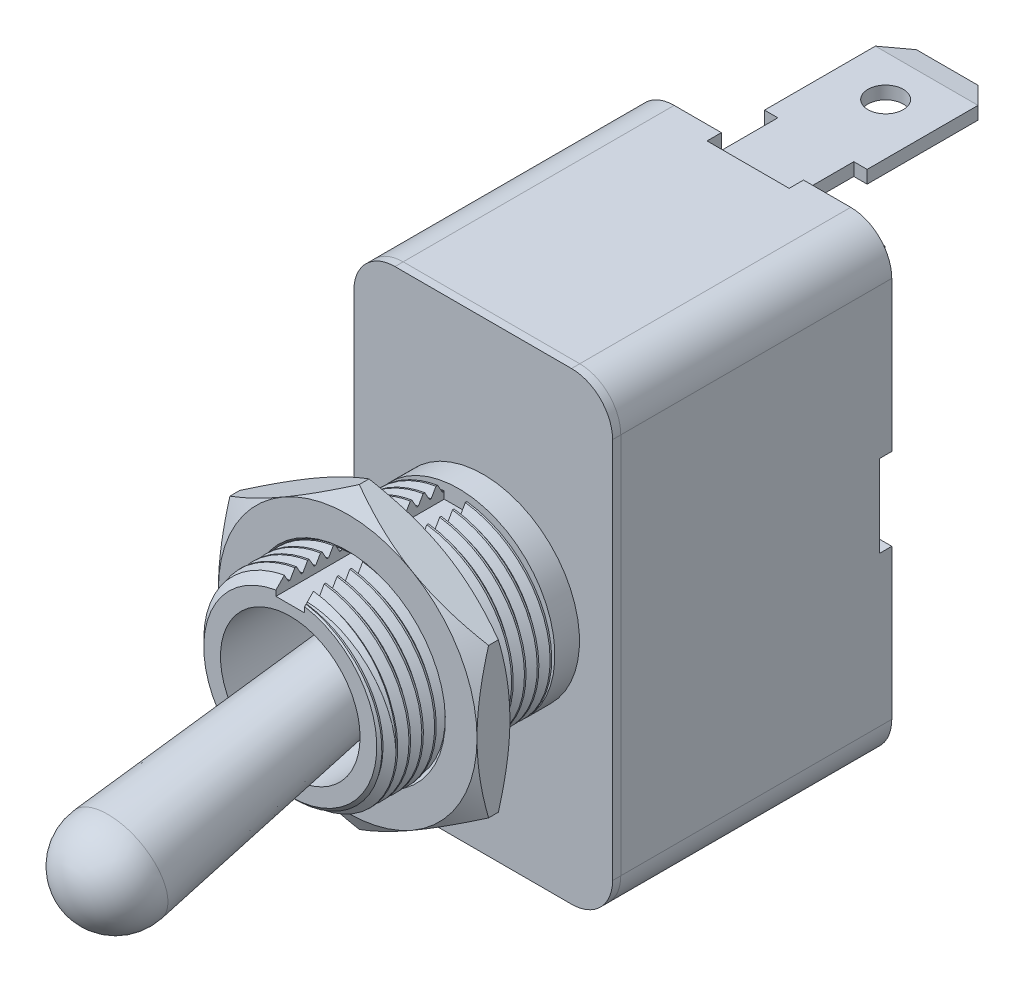
SolidWorks part; units mm, degrees
ref_plane "Front Plane" through (0, 0, 0) normal (0, 0, 1) x (1, 0, 0)
ref_plane "Top Plane" through (0, 0, 0) normal (0, 1, 0) x (1, 0, 0)
ref_plane "Right Plane" through (0, 0, 0) normal (1, 0, 0) x (0, 0, -1)
sketch "Sketch1" plane through (0, 0, 0) normal (0, 1, 0) x (1, 0, 0)
  line L0 (-9.144, 0) -> (9.144, 0) construction
  line L1 (14.351, -8.001) -> (-14.351, -8.001) construction
  line L2 (14.351, -8.001) -> (14.351, 8.001) construction
  line L3 (14.351, 8.001) -> (-14.351, 8.001) construction
  line L4 (-14.351, -8.001) -> (-14.351, 8.001) construction
  line L5 (14.351, -8.001) -> (-14.351, 8.001) construction
  line L6 (14.351, 8.001) -> (-14.351, -8.001) construction
  circle A0 centre (0, 0) radius 5.9531 construction
  point P0 (0, 0)
  point P8 (-5.9531, 0)
  point P9 (0, -5.9531)
  dimension "D3" = 9.144
  dimension "Thread OD" = 11.9062
  dimension "D1" = 28.702
  dimension "D2" = 16.002
sketch "Sketch2" plane through (0, 0, 0) normal (0, 0, 1) x (1, 0, 0)
  line L0 (0, 0) -> (0, 11.938) construction
  line L1 (14.351, 0) -> (-14.351, 0) construction
  line L2 (0, 11.938) -> (0, 26.162) construction
  line L3 (0, 0) -> (0, -17.272) construction
  line L4 (-14.351, 0) -> (14.351, 0) construction
  line L5 (0, -17.272) -> (0, -28.702) construction
  line L6 (-5.9531, 11.938) -> (5.9531, 11.938) construction
  line L7 (-3.048, 26.162) -> (3.048, 26.162) construction
  line L8 (-14.351, -17.272) -> (14.351, -17.272) construction
  line L9 (-5.9531, 11.938) -> (-5.9531, 11.1442) construction
  line L10 (-14.351, -28.702) -> (14.351, -28.702) construction
  point P15 (0, 1.524)
  dimension "D1" = 11.938
  dimension "D2" = 14.224
  dimension "D3" = 17.272
  dimension "D4" = 11.43
  dimension "D5" = 28.702
  dimension "D6" = 6.096
  dimension "Thread Height" = 10.414
  dimension "Thread Pitch" = 0.7937
sketch "Sketch3" plane through (0, 0, 0) normal (1, 0, 0) x (0, 0, -1)
  line L0 (-8.001, -17.272) -> (8.001, -17.272) construction
  line L1 (-8.001, 0) -> (8.001, 0) construction
  line L2 (-5.9531, 11.938) -> (5.9531, 11.938) construction
ref_plane "Plane1" through (0, 11.938, 0) normal (0, 1, 0) x (-1, 0, 0)
sketch "Sketch4" plane through (0, 11.938, 0) normal (0, 1, 0) x (-1, 0, 0)
  circle A0 centre (0, 0) radius 5.9531 construction
  circle A1 centre (0, 0) radius 5.9531
extrude "Boss-Extrude1" add sketch "Sketch4" against normal up to vertex (10.414 mm away) up to point (0, 1.524, 0)
sketch "Sketch5" plane through (0, 11.938, 0) normal (0, 1, 0) x (1, 0, 0)
  circle A1 centre (0, 0) radius 5.9531
  circle A2 centre (0, 0) radius 5.9531
  point P0 (-5.9531, 0)
  dimension "D1" = 0
curve "Helix/Spiral1" pitch 0.7937 height 11.2077 turns 14.12
sketch "Sketch6" plane through (0, 0, 0) normal (0, 0, 1) x (1, 0, 0)
  line L0 (-6.0391, 12.6821) -> (-6.0391, 11.8884) construction
  line L1 (-6.0391, 11.8884) -> (-5.3516, 12.2853) construction
  line L2 (-5.3516, 12.2853) -> (-6.0391, 12.6821) construction
  line L3 (-5.4376, 12.3349) -> (-5.4376, 12.2357)
  line L4 (-5.9531, 12.6325) -> (-5.9531, 11.938) construction
  line L5 (-5.3516, 12.2853) -> (-5.4376, 12.2853) construction
  line L6 (-5.9531, 12.2853) -> (-6.0391, 12.2853) construction
  line L7 (-5.4376, 12.2357) -> (-5.9961, 11.9132)
  line L8 (-5.9961, 11.9132) -> (-5.9961, 12.6573)
  line L9 (-5.9961, 12.6573) -> (-5.4376, 12.3349)
  point P13 (-5.9961, 12.2853)
  dimension "D1" = 0.7937
  dimension "D2" = 0.0992
sweep "Cut-Sweep1" cut profiles "Sketch6" path "Helix/Spiral1"
sketch "Sketch7" plane through (0, 11.938, 0) normal (0, 1, 0) x (1, 0, 0)
  circle A0 centre (0, 0) radius 5.3516
extrude "Cut-Extrude1" cut sketch "Sketch7" against normal up to vertex (10.414 mm away) draft 45 flip side to cut up to point (0, 1.524, 0)
sketch "Sketch8" plane through (0, 1.524, 0) normal (0, -1, 0) x (1, 0, 0)
  circle A2 centre (0, 0) radius 5.9531
  circle A3 centre (0, 0) radius 5.9531
  dimension "D2" = 0
extrude "Boss-Extrude2" add sketch "Sketch8" along normal up to vertex (1.524 mm away) up to point (0, 0, 0)
sketch "Sketch9" plane through (0, 0, 0) normal (0, -1, 0) x (1, 0, 0)
  line L0 (14.351, 8.001) -> (-14.351, 8.001) construction
  line L1 (-14.351, 8.001) -> (-14.351, -8.001) construction
  line L2 (14.351, -8.001) -> (-14.351, -8.001) construction
  line L3 (14.351, 8.001) -> (14.351, -8.001) construction
  line L4 (11.811, 8.001) -> (-11.811, 8.001)
  line L5 (-14.351, 5.461) -> (-14.351, -5.461)
  line L6 (11.811, -8.001) -> (-11.811, -8.001)
  line L7 (14.351, 5.461) -> (14.351, -5.461)
  arc A0 (11.811, 8.001) -> (14.351, 5.461) centre (11.811, 5.461) cw
  arc A1 (11.811, -8.001) -> (14.351, -5.461) centre (11.811, -5.461) ccw
  arc A2 (-14.351, -5.461) -> (-11.811, -8.001) centre (-11.811, -5.461) ccw
  arc A3 (-11.811, 8.001) -> (-14.351, 5.461) centre (-11.811, 5.461) ccw
  dimension "D1" = 2.54
extrude "Boss-Extrude3" add sketch "Sketch9" along normal blind 0.508
sketch "Sketch10" plane through (0, 11.938, 0) normal (0, 1, 0) x (1, 0, 0)
  line L0 (-5.9531, 0) -> (5.9531, 0) construction
  circle A0 centre (0, 0) radius 4.318
  dimension "D1" = 8.636
extrude "Cut-Extrude2" cut sketch "Sketch10" against normal up to surface (11.938 mm away) up to face at (0, 0, -5.9531)
sketch "Sketch11" plane through (0, 11.938, 0) normal (0, 1, 0) x (1, 0, 0)
  line L0 (4.9371, 0.889) -> (4.9371, -0.889)
  line L1 (4.9371, 0.889) -> (5.8864, 0.889)
  line L2 (4.9371, -0.889) -> (5.8864, -0.889)
  line L3 (0, 0) -> (5.9531, 0) construction
  circle A0 centre (0, 0) radius 5.9531 construction
  arc A1 (5.8864, -0.889) -> (5.8864, 0.889) centre (0, 0) ccw
  dimension "D1" = 1.016
  dimension "D2" = 1.778
extrude "Cut-Extrude3" cut sketch "Sketch11" against normal up to vertex (10.414 mm away) up to point (0, 1.524, 0)
sketch "Sketch12" plane through (0, 0, 0) normal (0, 0, 1) x (1, 0, 0)
  line L0 (0, 11.938) -> (0, 26.162) construction
  line L1 (0, 0) -> (0, 26.162) construction
  line L2 (-14.351, 0) -> (14.351, 0) construction
  line L3 (0, 4.826) -> (-2.2147, 4.826)
  line L4 (-2.2147, 4.826) -> (-3.0448, 22.9747)
  line L5 (0, 26.162) -> (0, 4.826)
  line L6 (-3.048, 26.162) -> (-3.048, 23.114) construction
  line L7 (-5.9531, 11.938) -> (5.9531, 11.938) construction
  arc A0 (0, 26.162) -> (-3.0448, 22.9747) centre (0, 23.114) ccw
  point P11 (-2.54, 11.938)
  dimension "D1" = 7.112
  dimension "D2" = 5.08
revolve "Revolve1" add sketch "Sketch12" angle 360 mid plane about L1
sketch "Sketch13" plane through (0, -0.508, 0) normal (0, -1, 0) x (1, 0, 0)
  line L4 (11.811, 8.001) -> (-11.811, 8.001)
  line L5 (-14.351, 5.461) -> (-14.351, -5.461)
  line L6 (-11.811, -8.001) -> (11.811, -8.001)
  line L7 (14.351, -5.461) -> (14.351, 5.461)
  line L8 (11.811, 8.001) -> (-11.811, 8.001)
  line L9 (-14.351, 5.461) -> (-14.351, -5.461)
  line L10 (-11.811, -8.001) -> (11.811, -8.001)
  line L11 (14.351, -5.461) -> (14.351, 5.461)
  arc A4 (14.351, 5.461) -> (11.811, 8.001) centre (11.811, 5.461) ccw
  arc A5 (-11.811, 8.001) -> (-14.351, 5.461) centre (-11.811, 5.461) ccw
  arc A6 (-14.351, -5.461) -> (-11.811, -8.001) centre (-11.811, -5.461) ccw
  arc A7 (11.811, -8.001) -> (14.351, -5.461) centre (11.811, -5.461) ccw
  arc A8 (14.351, 5.461) -> (11.811, 8.001) centre (11.811, 5.461) ccw
  arc A9 (-11.811, 8.001) -> (-14.351, 5.461) centre (-11.811, 5.461) ccw
  arc A10 (-14.351, -5.461) -> (-11.811, -8.001) centre (-11.811, -5.461) ccw
  arc A11 (11.811, -8.001) -> (14.351, -5.461) centre (11.811, -5.461) ccw
  dimension "D1" = 0
extrude "Boss-Extrude4" add sketch "Sketch13" along normal up to vertex (16.764 mm away) separate body up to point (0, -17.272, 0)
sketch "Sketch14" plane through (0, -17.272, 0) normal (0, -1, 0) x (1, 0, 0)
  line L0 (0, -8.001) -> (0, 8.001) construction
  line L1 (-14.351, 0) -> (14.351, 0) construction
  line L2 (14.351, 8.001) -> (-14.351, 8.001) construction
  line L4 (-14.351, 2.54) -> (-5.969, 2.54)
  line L5 (-14.351, 2.54) -> (-14.351, -2.54)
  line L6 (-14.351, -2.54) -> (-5.969, -2.54)
  line L7 (-5.969, 2.54) -> (-5.969, -2.54)
  line L8 (-2.54, 8.001) -> (2.54, 8.001) construction
  line L9 (-2.54, 8.001) -> (-2.54, -8.001) construction
  line L10 (-2.54, -8.001) -> (2.54, -8.001) construction
  line L14 (2.54, 8.001) -> (2.54, -8.001) construction
  line L15 (-14.351, 5.461) -> (-14.351, -5.461) construction
  line L16 (5.969, 2.54) -> (5.969, -2.54)
  line L17 (14.351, -2.54) -> (5.969, -2.54)
  line L18 (14.351, 2.54) -> (14.351, -2.54)
  line L19 (14.351, 2.54) -> (5.969, 2.54)
  dimension "D2" = 5.08
  dimension "D3" = 8.382
  dimension "D1" = 5.08
extrude "Cut-Extrude4" cut sketch "Sketch14" against normal blind 0.889
sketch "Sketch15" plane through (0, -17.272, 0) normal (0, -1, 0) x (1, 0, 0)
  line L1 (-2.54, 8.001) -> (-2.54, -8.001) construction
  line L2 (-2.54, 8.001) -> (2.54, 8.001) construction
  line L3 (2.54, 8.001) -> (2.54, -8.001) construction
  line L4 (-2.54, -8.001) -> (2.54, -8.001) construction
  line L5 (-2.54, 8.001) -> (-2.54, -8.001)
  line L6 (-2.54, 8.001) -> (2.54, 8.001)
  line L7 (2.54, 8.001) -> (2.54, -8.001)
  line L9 (-2.54, -8.001) -> (2.54, -8.001)
extrude "Cut-Extrude5" cut sketch "Sketch15" against normal blind 0.762
sketch "Sketch16" plane through (0, -16.383, 0) normal (0, -1, 0) x (1, 0, 0)
  line L0 (13.589, 2.3495) -> (13.589, -2.3495)
  line L1 (7.239, 2.3495) -> (13.589, 2.3495)
  line L2 (7.239, 2.3495) -> (7.239, -2.3495)
  line L3 (7.239, -2.3495) -> (13.589, -2.3495)
  line L4 (7.239, 0) -> (13.589, 0) construction
  circle A0 centre (9.144, 0) radius 1.524 construction
  dimension "D1" = 3.048
  dimension "D2" = 4.699
  dimension "D3" = 6.35
  dimension "D4" = 1.905
extrude "Boss-Extrude5" add sketch "Sketch16" along normal blind 0.7937 separate body
sketch "Sketch17" plane through (13.589, 0, 0) normal (-1, 0, 0) x (0, 0, 1)
  line L0 (-3.175, -28.702) -> (3.175, -28.702)
  line L1 (0, -16.383) -> (0, -28.702) construction
  line L4 (2.3495, -16.383) -> (-2.3495, -16.383)
  line L5 (-2.3495, -16.383) -> (-2.3495, -17.1767)
  line L6 (-2.3495, -17.1767) -> (2.3495, -17.1767)
  line L7 (2.3495, -17.1767) -> (2.3495, -16.383)
  line L8 (2.3495, -16.383) -> (-2.3495, -16.383)
  line L9 (-2.3495, -16.383) -> (-2.3495, -20.574)
  line L11 (2.3495, -20.574) -> (2.3495, -16.383)
  line L12 (-3.175, -20.574) -> (-2.3495, -20.574)
  line L13 (-3.175, -20.574) -> (-3.175, -28.702)
  line L16 (3.175, -20.574) -> (3.175, -28.702)
  line L17 (3.175, -20.574) -> (2.3495, -20.574)
  circle A1 centre (0, -24.892) radius 1.0922
  dimension "D2" = 2.1844
  dimension "D3" = 6.35
  dimension "D4" = 8.128
  dimension "D8" = 3.81
  dimension "D1" = 0
extrude "Boss-Extrude6" add sketch "Sketch17" along normal blind 0.7937
chamfer "Chamfer1" distance 1.27 distance2 1.27 2 edges at (13.1921, -28.702, -3.175) (13.1921, -28.702, 3.175)
chamfer "Chamfer2" distance 1.27 distance2 0.1905 2 edges at (13.589, -28.702, 0) (12.7953, -28.702, 0)
mirror "Mirror1" [suppressed] about plane through (0, 0, 0) normal (1, 0, 0)
sketch "Sketch18" plane through (0, -16.51, 0) normal (0, -1, 0) x (1, 0, 0)
  line L0 (-2.3495, -4.445) -> (-2.3495, 1.905)
  line L1 (2.3495, -4.445) -> (2.3495, 1.905)
  line L2 (2.3495, 1.905) -> (-2.3495, 1.905)
  line L3 (0, 1.905) -> (0, -4.445) construction
  line L4 (-2.3495, -4.445) -> (2.3495, -4.445)
  circle A0 centre (0, 0) radius 1.524 construction
  dimension "D3" = 3.048
  dimension "D1" = 6.35
  dimension "D2" = 4.699
  dimension "D4" = 1.905
extrude "Boss-Extrude7" add sketch "Sketch18" along normal blind 0.7937 separate body
sketch "Sketch19" plane through (0, 0, -4.445) normal (0, 0, 1) x (1, 0, 0)
  line L0 (3.175, -28.702) -> (-3.175, -28.702)
  line L1 (-3.175, -28.702) -> (-3.175, -20.574)
  line L2 (-3.175, -20.574) -> (-2.3495, -20.574)
  line L4 (2.3495, -16.51) -> (-2.3495, -16.51)
  line L5 (-2.3495, -16.51) -> (-2.3495, -17.3038)
  line L6 (-2.3495, -17.3038) -> (2.3495, -17.3038)
  line L7 (2.3495, -17.3038) -> (2.3495, -16.51)
  line L8 (2.3495, -16.51) -> (-2.3495, -16.51)
  line L9 (-2.3495, -16.51) -> (-2.3495, -20.574)
  line L11 (2.3495, -20.574) -> (2.3495, -16.51)
  line L13 (0, -28.702) -> (0, -16.51) construction
  line L17 (3.175, -20.574) -> (2.3495, -20.574)
  line L18 (3.175, -28.702) -> (3.175, -20.574)
  circle A1 centre (0, -24.892) radius 1.0922
  dimension "D2" = 2.1844
  dimension "D3" = 6.35
  dimension "D5" = 8.128
  dimension "D8" = 3.81
  dimension "D1" = 0
extrude "Boss-Extrude8" add sketch "Sketch19" along normal blind 0.7937
chamfer "Chamfer3" distance 1.27 distance2 1.27 2 edges at (3.175, -28.702, -4.0481) (-3.175, -28.702, -4.0481)
chamfer "Chamfer4" distance 0.1905 distance2 1.27 2 edges at (0, -28.702, -3.6512) (0, -28.702, -4.445)
sketch "Sketch20" plane through (0, 11.938, 0) normal (0, 1, 0) x (1, 0, 0)
  line L1 (4.6194, 8.001) -> (-4.6194, 8.001)
  line L2 (-4.6194, 8.001) -> (-9.2388, 0)
  line L3 (-9.2388, 0) -> (-4.6194, -8.001)
  line L4 (-4.6194, -8.001) -> (4.6194, -8.001)
  line L5 (4.6194, -8.001) -> (9.2388, 0)
  line L6 (9.2388, 0) -> (4.6194, 8.001)
  circle A0 centre (0, 0) radius 8.001 construction
  circle A1 centre (0, 0) radius 5.4376
  point P10 (-8.001, 0)
  dimension "D1" = 16.002
extrude "Boss-Extrude9" add sketch "Sketch20" along normal blind 2.032 from offset 5.585 separate body offset against normal yes
sketch "Sketch21" plane through (0, 0, 0) normal (0, 0, 1) x (1, 0, 0)
  line L0 (-5.4376, 8.385) -> (-5.4376, 7.7835)
  line L1 (-5.4376, 7.7835) -> (-6.0391, 8.385)
  line L2 (-6.0391, 8.385) -> (-5.4376, 8.385)
  line L5 (-6.0391, 12.6821) -> (-6.0391, 11.8884) construction
  line L6 (0, 8.385) -> (0, 6.353) construction
  line L7 (5.4376, 8.385) -> (-5.4376, 8.385) construction
  line L8 (-5.4376, 6.353) -> (5.4376, 6.353) construction
  line L9 (-9.2388, 8.385) -> (-8.001, 8.385)
  line L10 (-8.001, 8.385) -> (-9.2388, 7.6704)
  line L11 (-9.2388, 7.6704) -> (-9.2388, 8.385)
  line L12 (-5.4376, 6.9545) -> (-5.4376, 6.353)
  line L13 (-5.4376, 6.353) -> (-6.0391, 6.353)
  line L14 (-6.0391, 6.353) -> (-5.4376, 6.9545)
  line L15 (-9.2388, 6.353) -> (-9.2388, 7.0676)
  line L16 (-9.2388, 7.0676) -> (-8.001, 6.353)
  line L17 (-8.001, 6.353) -> (-9.2388, 6.353)
  dimension "D1" = 45
  dimension "D2" = 30
revolve "Cut-Revolve1" cut sketch "Sketch21" angle 360 mid plane about L6
move or copy body "Body-Move/Copy1" bodies to move or copy 115 109 129 122 126 131 copy no rotation origin (2.678, -3.4086, 0.7306) rotation axis (0.5774, 0.5774, 0.5774) rotation angle 120
sketch "Sketch22" plane through (0, 0, 0) normal (1, 0, 0) x (0, 0, -1)
  arc A0 (-27.1139, -3.0417) -> (-27.1139, -9.1314) centre (-27.2532, -6.0865) ccw construction
  point P0 (-30.3012, -6.0865)
sketch "Sketch23" plane through (0, 0, 0) normal (1, 0, 0) x (0, 0, -1)
  line L0 (-15.9587, -3.552) -> (-27.1139, -3.0417)
  line L1 (-8.9652, -3.8718) -> (-27.1139, -3.0417) construction
  line L2 (-27.1139, -9.1314) -> (-15.8818, -8.6176)
  line L3 (-27.1139, -9.1314) -> (-8.9652, -8.3012) construction
  arc A0 (-27.1139, -3.0417) -> (-27.1139, -9.1314) centre (-27.2532, -6.0865) ccw
  spline S0 degree 3 poles (-15.9913, -1.847) (-15.9819, -2.246) (-15.9729, -2.736) (-15.9586, -3.5521) (-15.9538, -3.8403) (-15.9441, -4.442) (-15.9393, -4.7492) (-15.93, -5.3761) (-15.9253, -5.6983) (-15.9164, -6.344) (-15.9119, -6.6638) (-15.9026, -7.2971) (-15.8978, -7.6136) (-15.8883, -8.225) (-15.8835, -8.5186) (-15.8741, -9.0819) (-15.8694, -9.3541) (-15.8603, -9.8584) (-15.856, -10.0907) (-15.847, -10.5169) (-15.8424, -10.7122) (-15.833, -11.0509) (-15.8283, -11.1954) (-15.8189, -11.4352) (-15.8142, -11.5308) (-15.805, -11.6651) (-15.8005, -11.7049) (-15.7917, -11.73) (-15.7873, -11.7148) (-15.7782, -11.6303) (-15.7736, -11.5616) (-15.7644, -11.371) (-15.7596, -11.2477) (-15.7504, -10.9558) (-15.7458, -10.7868) (-15.7369, -10.4025) (-15.7325, -10.1853) (-15.7238, -9.7197) (-15.7194, -9.47) (-15.7103, -8.9366) (-15.7056, -8.6511) (-15.6964, -8.066) (-15.6919, -7.7644) (-15.6828, -7.1429) (-15.6782, -6.821) (-15.6696, -6.1819) (-15.6654, -5.8621) (-15.6567, -5.222) (-15.6521, -4.9) (-15.6431, -4.2781) (-15.6385, -3.9757) (-15.6295, -3.3879) (-15.6249, -3.1009) (-15.616, -2.5645) (-15.6116, -2.3127) (-15.6032, -1.8416) (-15.5989, -1.6212) (-15.5901, -1.2283) (-15.5857, -1.0539) (-15.5767, -0.7494) (-15.5721, -0.6186) (-15.5632, -0.4108) (-15.5587, -0.3325) (-15.5544, -0.2797) knots 0 0 0 0 0.0625 0.0625 0.09375 0.09375 0.125 0.125 0.15625 0.15625 0.1875 0.1875 0.21875 0.21875 0.25 0.25 0.28125 0.28125 0.3125 0.3125 0.34375 0.34375 0.375 0.375 0.40625 0.40625 0.4375 0.4375 0.46875 0.46875 0.5 0.5 0.53125 0.53125 0.5625 0.5625 0.59375 0.59375 0.625 0.625 0.65625 0.65625 0.6875 0.6875 0.71875 0.71875 0.75 0.75 0.78125 0.78125 0.8125 0.8125 0.84375 0.84375 0.875 0.875 0.90625 0.90625 0.9375 0.9375 0.96875 0.96875 1 1 1 1 construction
move or copy body "Body-Move/Copy2" bodies to move or copy 134 copy no rotation origin (0, -6.0865, 8.8318) rotation axis (1, 0, 0) rotation angle 11.5
move or copy body "Body-Move/Copy3" [suppressed] bodies to move or copy 139 copy yes number of copies 1 rotation origin (0, -5.8577, 8.985) rotation axis (-1, 0, 0) rotation angle 24.5
sketch "Sketch24" [suppressed] plane through (0, 0, 0) normal (1, 0, 0) x (0, 0, -1)
  line L0 (-16.0772, -1.8434) -> (-26.0691, 0.9499)
  line L1 (-8.5723, -3.9415) -> (-26.0691, 0.9499) construction
  line L2 (-27.439, -4.9837) -> (-9.5687, -8.2574) construction
  line L3 (-27.439, -4.9837) -> (-16.0772, -7.0651)
  line L4 (-27.439, -4.9837) -> (-9.5687, -8.2574) construction
  line L5 (-16.0772, -0.8093) -> (-16.0772, -11.4382) construction
  line L6 (-16.0772, -6.1237) -> (-30.3012, -6.1237) construction
  line L7 (-28.9685, 1.9889) -> (-16.0772, -4.0224) construction
  line L8 (-28.9685, -14.2363) -> (-16.0772, -8.225) construction
  line L9 (-16.0772, -4.0224) -> (-16.0772, -8.225) construction
  arc A0 (-26.0691, 0.9499) -> (-27.439, -4.9837) centre (-26.8898, -1.9856) ccw
  arc A1 (-28.9685, -14.2363) -> (-28.9685, 1.9889) centre (-4.9423, -6.1237) cw construction
  point P14 (-16.0772, -6.1237)
  dimension "D1" = 14.224
  dimension "D2" = 25
  dimension "D3" = 25
  dimension "D4" = 4.2026
equation "\"D4@Helix/Spiral1\" = \"Thread Pitch@Sketch2\""
equation "\"D3@Helix/Spiral1\" = \"D4@Helix/Spiral1\" + \"Thread Height@Sketch2\""
equation "\"D1@Sketch6\" = \"D4@Helix/Spiral1\""
equation "\"D2@Sketch6\" = \"D1@Sketch6\" / 8"
